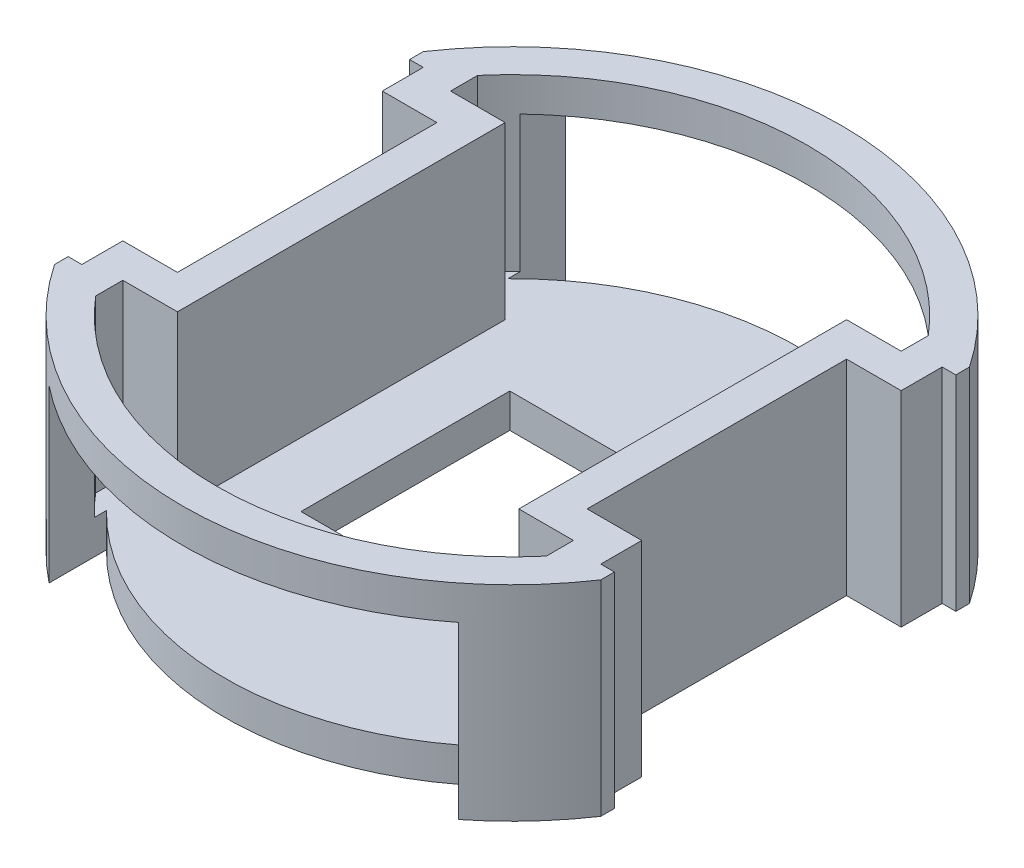
SolidWorks part; units mm, degrees
ref_plane "前视" through (0, 0, 0) normal (0, 0, 1) x (1, 0, 0)
ref_plane "上视" through (0, 0, 0) normal (0, 1, 0) x (1, 0, 0)
ref_plane "右视" through (0, 0, 0) normal (1, 0, 0) x (0, 0, -1)
sketch "草图1" plane through (0, 0, 0) normal (0, 1, 0) x (1, 0, 0)
  line L0 (-40, -27) -> (40, -27) construction
  line L1 (-49.6639, 0) -> (49.1988, 0) construction
  line L2 (0, 47.8291) -> (0, -48.5442) construction
  line L3 (-40, -27) -> (-40, -25)
  line L4 (-40, -25) -> (-38, -25)
  line L5 (-30, -19) -> (-30, 19)
  line L6 (-40, 27) -> (-40, 25)
  line L7 (-40, 25) -> (-38, 25)
  line L8 (40, -27) -> (40, -25)
  line L9 (40, -25) -> (38, -25)
  line L10 (30, -19) -> (30, 19)
  line L11 (40, 25) -> (38, 25)
  line L12 (40, 27) -> (40, 25)
  line L13 (-38, -25) -> (-38, -19)
  line L14 (-38, -19) -> (-30, -19)
  line L15 (-38, 19) -> (-30, 19)
  line L16 (-38, 25) -> (-38, 19)
  line L17 (38, -25) -> (38, -19)
  line L18 (38, -19) -> (30, -19)
  line L19 (38, 19) -> (30, 19)
  line L20 (38, 25) -> (38, 19)
  arc A0 (-40, -27) -> (40, -27) centre (0, 0) ccw
  arc A1 (40, 27) -> (-40, 27) centre (0, 0) ccw
  point P15 (-30, 0)
  dimension "D1" = 60
  dimension "D2" = 27
  dimension "D3" = 2
  dimension "D4" = 8
  dimension "D5" = 2
  dimension "D6" = 6
extrude "凸台-拉伸1" add sketch "草图1" along normal blind 30
sketch "草图2" plane through (0, 0, 0) normal (0, 0, 1) x (1, 0, 0)
  line L0 (0, 0) -> (0, -76.7326) construction
  line L1 (-49.6639, 0) -> (49.1988, 0) construction
shell "抽壳1" thickness 5 removed face at (0, 30, 0)
sketch "草图3" plane through (0, 0, 0) normal (0, -1, 0) x (1, 0, 0)
  line L0 (30, 0) -> (-30, 0) construction
  line L1 (30, 19) -> (30, -19) construction
  line L2 (-30, -19) -> (-30, 19) construction
  line L3 (0, -48.2597) -> (0, 48.2597) construction
  line L4 (-30, 29.3939) -> (-30, 37.8021)
  line L5 (30, 29.3939) -> (30, 37.8021)
  line L6 (-30, -29.3939) -> (-30, -37.8021)
  line L7 (30, -29.3939) -> (30, -37.8021)
  line L9 (-15.616, 15.2905) -> (15.616, 15.2905)
  line L10 (-15.616, 15.2905) -> (-15.616, -15.2905)
  line L11 (-15.616, -15.2905) -> (15.616, -15.2905)
  line L12 (15.616, 15.2905) -> (15.616, -15.2905)
  line L13 (-15.616, 15.2905) -> (15.616, -15.2905) construction
  line L14 (-15.616, -15.2905) -> (15.616, 15.2905) construction
  arc A0 (-40, -27) -> (40, -27) centre (0, 0) ccw construction
  arc A1 (40, 27) -> (-40, 27) centre (0, 0) ccw construction
  arc A2 (30, 29.3939) -> (-30, 29.3939) centre (0, 0) ccw
  arc A3 (30, 37.8021) -> (-30, 37.8021) centre (0, 0) ccw
  arc A4 (30, -37.8021) -> (-30, -37.8021) centre (0, 0) cw
  arc A5 (30, -29.3939) -> (-30, -29.3939) centre (0, 0) cw
extrude "切除-拉伸1" cut sketch "草图3" against normal blind 25
